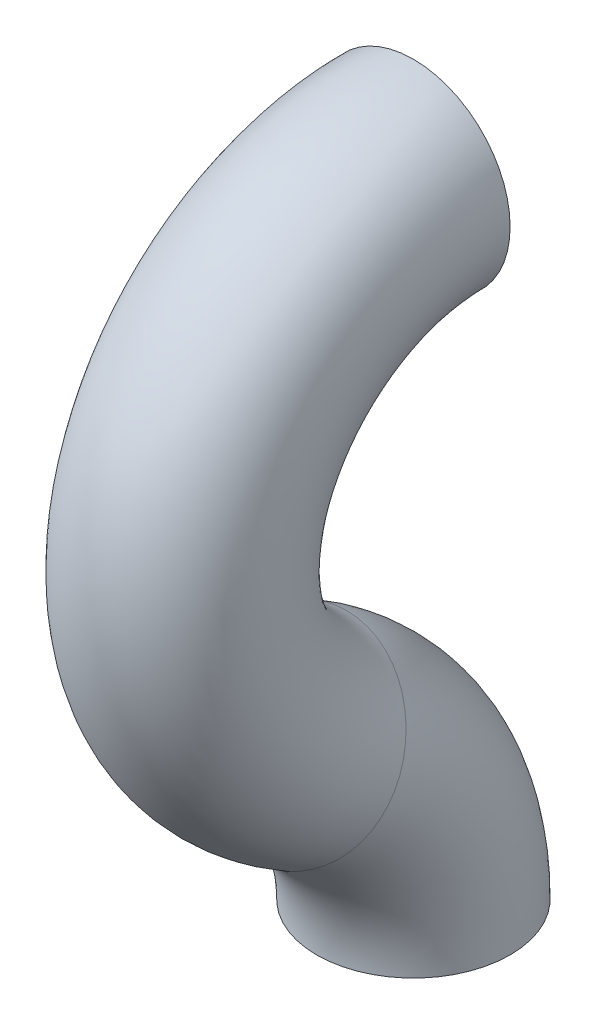
SolidWorks part; units mm, degrees
ref_plane "Front Plane" through (0, 0, 0) normal (0, 0, 1) x (1, 0, 0)
ref_plane "Top Plane" through (0, 0, 0) normal (0, 1, 0) x (1, 0, 0)
ref_plane "Right Plane" through (0, 0, 0) normal (1, 0, 0) x (0, 0, -1)
sketch "Sketch1" plane through (0, 0, 0) normal (1, 0, 0) x (0, 0, -1)
  line L0 (0, 0) -> (0, -37.0564) construction
  line L1 (0, 150) -> (64.3168, 150) construction
  line L2 (0, 150) -> (0, 0) construction
  arc A0 (0, 0) -> (-27.4519, 47.5481) centre (-54.9038, 0) ccw
  arc A1 (-27.4519, 47.5481) -> (0, 150) centre (0, 95.0962) cw
  dimension "D1" = 150
sketch "Sketch2" plane through (0, 0, 0) normal (0, 1, 0) x (1, 0, 0)
  circle A0 centre (0, 0) radius 23
  dimension "D1" = 46
sweep "Sweep1" add profiles "Sketch2" path "Sketch1"
